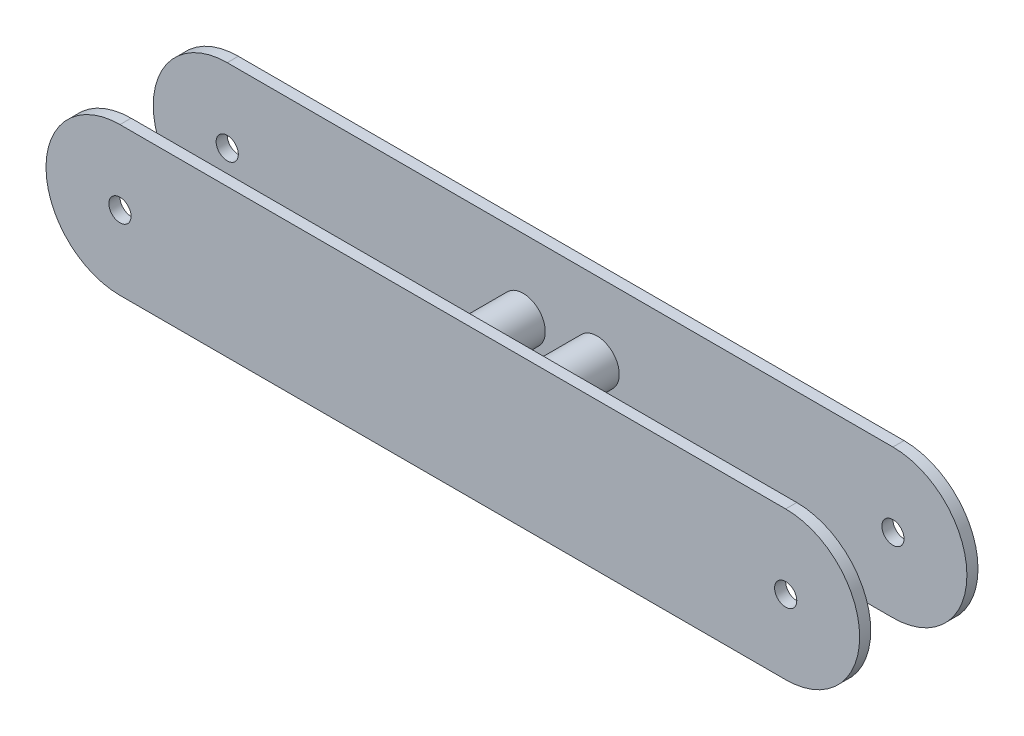
SolidWorks part; units mm, degrees
ref_plane "Front Plane" through (0, 0, 0) normal (0, 0, 1) x (1, 0, 0)
ref_plane "Top Plane" through (0, 0, 0) normal (0, 1, 0) x (1, 0, 0)
ref_plane "Right Plane" through (0, 0, 0) normal (1, 0, 0) x (0, 0, -1)
sketch "Sketch1" plane through (0, 0, 0) normal (0, 0, 1) x (1, 0, 0)
  line L1 (-3.7451, 2.0995) -> (86.2549, 2.0995)
  line L2 (-3.7451, 2.0995) -> (-3.7451, -17.9005)
  line L3 (-3.7451, -17.9005) -> (86.2549, -17.9005)
  line L4 (86.2549, 2.0995) -> (86.2549, -17.9005)
  arc A0 (-3.7451, 2.0995) -> (-3.7451, -17.9005) centre (-3.7451, -7.9005) ccw
  arc A1 (86.2549, 2.0995) -> (86.2549, -17.9005) centre (86.2549, -7.9005) cw
  dimension "D1" = 90
  dimension "D2" = 20
extrude "Boss-Extrude2" add sketch "Sketch1" along normal blind 16 contours L2 A0 | L4 L1 L2 L3 | A1 L4 region at (41.2549, -7.9005, 0) region at (-7.9893, -7.9005, 0) region at (90.499, -7.9005, 0)
sketch "Sketch2" plane through (0, 0, 16) normal (0, 0, 1) x (1, 0, 0)
  circle A0 centre (-3.7451, -7.9005) radius 1.5
  circle A1 centre (86.2549, -7.9005) radius 1.5
extrude "Cut-Extrude1" cut sketch "Sketch2" against normal blind 16
sketch "Sketch3" plane through (0, 2.0995, 0) normal (0, 1, 0) x (1, 0, 0)
  line L0 (-3.7451, -16) -> (86.2549, -16) construction
  line L1 (-13.7605, -14.5) -> (96.2762, -14.5)
  line L2 (-13.7605, -14.5) -> (-13.7605, -1.5)
  line L3 (-13.7605, -1.5) -> (96.2762, -1.5)
  line L4 (96.2762, -14.5) -> (96.2762, -1.5)
  line L5 (-3.7451, 0) -> (86.2549, 0) construction
  dimension "D1" = 1.5
  dimension "D2" = 1.5
extrude "Cut-Extrude2" cut sketch "Sketch3" against normal blind 23
sketch "Sketch4" plane through (0, 0, 0) normal (0, 0, -1) x (-1, 0, 0)
  line L0 (3.7451, 2.0995) -> (-86.2549, 2.0995) construction
  circle A0 centre (-36.2549, -7.9005) radius 3
  circle A1 centre (-46.2549, -7.9005) radius 3
  arc A2 (-86.2549, 2.0995) -> (-86.2549, -17.9005) centre (-86.2549, -7.9005) ccw construction
  dimension "D4" = 40
  dimension "D1" = 10
  dimension "D2" = 10
  dimension "D3" = 10
extrude "Boss-Extrude3" add sketch "Sketch4" against normal blind 16
